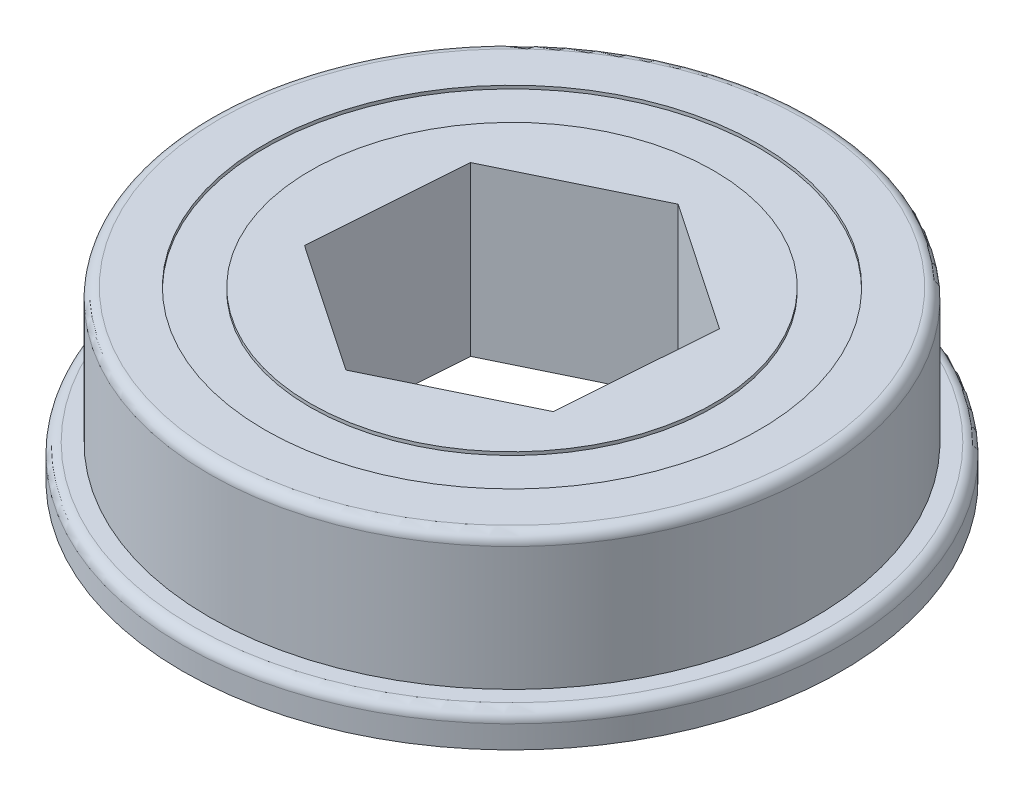
SolidWorks part; units mm, degrees
ref_plane "Front Plane" through (0, 0, 0) normal (0, 0, 1) x (1, 0, 0)
ref_plane "Top Plane" through (0, 0, 0) normal (0, 1, 0) x (1, 0, 0)
ref_plane "Right Plane" through (0, 0, 0) normal (1, 0, 0) x (0, 0, -1)
sketch "Sketch1" plane through (0, 0, 0) normal (0, 1, 0) x (1, 0, 0)
  line L1 (6.069, -4.1147) -> (6.5979, 3.1986)
  line L2 (6.5979, 3.1986) -> (0.5289, 7.3132)
  line L3 (0.5289, 7.3132) -> (-6.069, 4.1147)
  line L4 (-6.069, 4.1147) -> (-6.5979, -3.1986)
  line L5 (-6.5979, -3.1986) -> (-0.5289, -7.3132)
  line L6 (-0.5289, -7.3132) -> (6.069, -4.1147)
  circle A1 centre (0, 0) radius 6.35 construction
  circle A2 centre (0, 0) radius 9.525
  dimension "D2" = 12.7
  dimension "D3" = 19.05
extrude "Boss-Extrude1" add sketch "Sketch1" along normal blind 7.9248
ref_plane "Mid_Plane" through (0, 3.9624, 0) normal (0, -1, 0) x (-1, 0, 0)
sketch "Sketch2" plane through (0, 3.9624, 0) normal (0, 1, 0) x (1, 0, 0)
  circle A0 centre (0, 0) radius 9.525
  circle A1 centre (0, 0) radius 11.6745
extrude "Boss-Extrude2" add sketch "Sketch2" along normal blind 3.81 and the other way blind 3.81 separate body
sketch "Sketch3" plane through (0, 0, 0) normal (0, 1, 0) x (1, 0, 0)
  circle A0 centre (0, 0) radius 14.2875
  circle A1 centre (0, 0) radius 11.6745 construction
  circle A2 centre (0, 0) radius 11.6745
  dimension "D1" = 28.575
extrude "Boss-Extrude4" add sketch "Sketch3" along normal blind 7.9248
sketch "Sketch4" plane through (0, 0, 0) normal (0, 1, 0) x (1, 0, 0)
  circle A0 centre (0, 0) radius 15.56
  circle A1 centre (0, 0) radius 14.2875 construction
  circle A2 centre (0, 0) radius 14.2875
  dimension "D1" = 31.1201
extrude "Boss-Extrude5" add sketch "Sketch4" along normal blind 1.5748
fillet "Fillet1" radius 0.508 2 edges at (0, 1.5748, 15.56) (0, 7.9248, 14.2875)
ref_axis "Center_Axis" through (0, 27.8576, 0) along (0, -1, 0)
